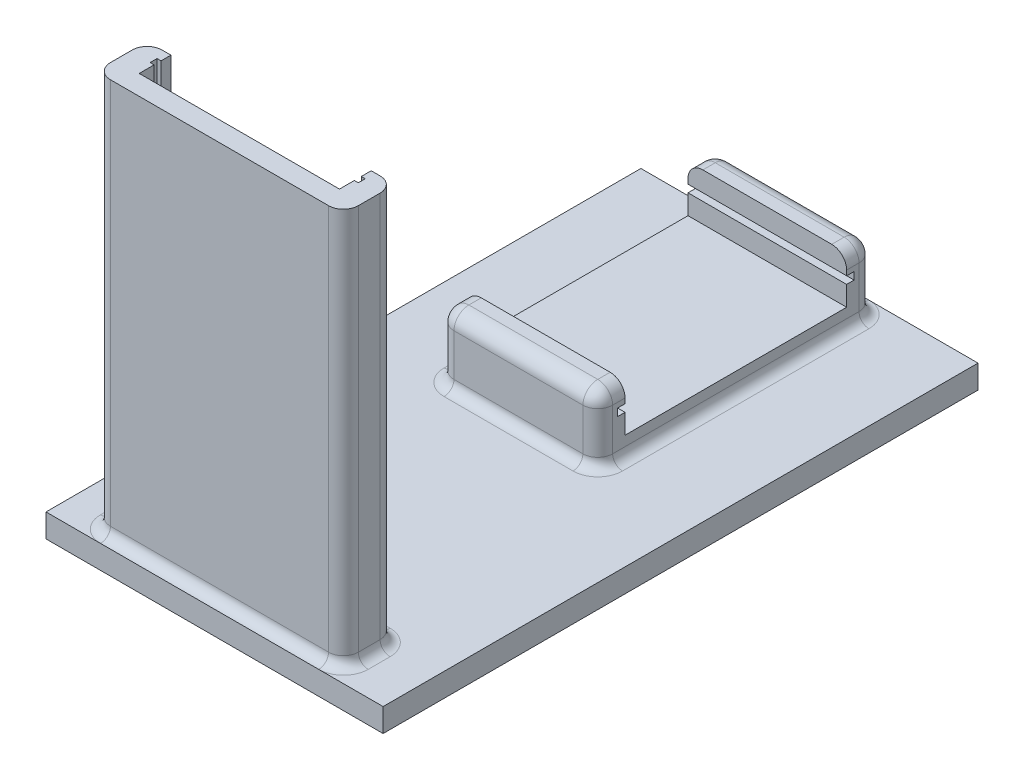
SolidWorks part; units mm, degrees
material "Melamine resin"
ref_plane "Front Plane" through (0, 0, 0) normal (0, 0, 1) x (1, 0, 0)
ref_plane "Top Plane" through (0, 0, 0) normal (0, 1, 0) x (1, 0, 0)
ref_plane "Right Plane" through (0, 0, 0) normal (1, 0, 0) x (0, 0, -1)
sketch "Sketch2" plane through (0, 0, 0) normal (0, 1, 0) x (1, 0, 0)
  line L1 (0, 0) -> (88.9, 0)
  line L2 (0, 0) -> (0, 152.4)
  line L3 (0, 152.4) -> (88.9, 152.4)
  line L10 (88.9, 152.4) -> (88.9, 0)
  dimension "D1" = 152.4
  dimension "D2" = 88.9
extrude "Boss-Extrude1" add sketch "Sketch2" along normal blind 5.9944 contours L3 L10 L1 L2
sketch "Sketch4" plane through (0, 5.9944, 0) normal (0, 1, 0) x (1, 0, 0)
  line L0 (0, 0) -> (0, 152.4) construction
  line L1 (0, 0) -> (88.9, 0) construction
  circle A0 centre (45.72, 109.8713) radius 2.7305
  circle A1 centre (45.72, 33.6713) radius 2.7305
  dimension "D3" = 5.461
  dimension "D4" = 5.461
  dimension "D1" = 76.2
  dimension "D2" = 45.72
  dimension "D5" = 33.6713
extrude "Cut-Extrude2" cut sketch "Sketch4" against normal through all both
sketch "Sketch5" plane through (0, 5.9944, 0) normal (0, 1, 0) x (1, 0, 0)
  line L0 (0, 152.4) -> (88.9, 152.4) construction
  line L1 (12.7, 15.748) -> (76.2, 15.748)
  line L2 (12.7, 15.748) -> (12.7, 2.54)
  line L3 (12.7, 2.54) -> (76.2, 2.54)
  line L4 (76.2, 15.748) -> (76.2, 2.54)
  line L5 (18.796, 7.62) -> (70.104, 7.62)
  line L6 (18.796, 7.62) -> (18.796, 15.748)
  line L7 (18.796, 15.748) -> (70.104, 15.748)
  line L8 (70.104, 7.62) -> (70.104, 15.748)
  line L9 (17.78, 13.208) -> (71.12, 13.208)
  line L10 (17.78, 13.208) -> (17.78, 11.43)
  line L11 (17.78, 11.43) -> (71.12, 11.43)
  line L12 (71.12, 13.208) -> (71.12, 11.43)
  line L13 (0, 0) -> (88.9, 0) construction
  point P16 (44.45, 152.4)
  point P17 (44.45, 15.748)
  dimension "D1" = 53.34
  dimension "D2" = 1.016
  dimension "D3" = 1.016
  dimension "D4" = 3.81
  dimension "D5" = 2.54
  dimension "D6" = 5.08
  dimension "D7" = 5.08
  dimension "D8" = 1.778
  dimension "D9" = 2.54
  dimension "D10" = 5.08
extrude "Boss-Extrude2" add sketch "Sketch5" along normal blind 101.6 contours L9 L12 L11 L8 L5 L6 L10 L1 L2 L3 L4 region at (44.45, 5.9944, -6.5828)
fillet "Fillet1" radius 3.81 4 edges at (12.7, 56.7944, -2.54) (12.7, 56.7944, -15.748) (76.2, 56.7944, -2.54) (76.2, 56.7944, -15.748)
fillet "Fillet2" radius 2.54 9 edges at (17.653, 5.9944, -15.748) (13.8159, 5.9944, -14.6321) (12.7, 5.9944, -9.144) (13.8159, 5.9944, -3.6559) (71.247, 5.9944, -15.748) (75.0841, 5.9944, -14.6321) (76.2, 5.9944, -9.144) (75.0841, 5.9944, -3.6559) (44.45, 5.9944, -2.54)
ref_plane "Plane1" through (44.45, 0, 0) normal (-1, 0, 0) x (0, 0, 1)
sketch "Sketch6" plane through (44.45, 0, 0) normal (-1, 0, 0) x (0, 0, 1)
  line L0 (0, 5.9944) -> (-152.4, 5.9944) construction
  line L1 (0, 5.9944) -> (-152.4, 5.9944)
  line L3 (-149.86, 5.9944) -> (-79.121, 5.9944)
  line L4 (-149.86, 5.9944) -> (-149.86, 23.1394)
  line L5 (-149.86, 23.1394) -> (-79.121, 23.1394)
  line L6 (-79.121, 5.9944) -> (-79.121, 23.1394)
  line L7 (-142.875, 23.1394) -> (-86.106, 23.1394)
  line L8 (-142.875, 23.1394) -> (-142.875, 11.0744)
  line L9 (-142.875, 11.0744) -> (-86.106, 11.0744)
  line L10 (-86.106, 23.1394) -> (-86.106, 11.0744)
  line L11 (-144.78, 18.0594) -> (-84.201, 18.0594)
  line L12 (-144.78, 18.0594) -> (-144.78, 16.1544)
  line L13 (-144.78, 16.1544) -> (-84.201, 16.1544)
  line L14 (-84.201, 18.0594) -> (-84.201, 16.1544)
  line L15 (-152.4, 5.9944) -> (-152.4, 0) construction
  dimension "D1" = 60.579
  dimension "D2" = 1.905
  dimension "D3" = 1.905
  dimension "D4" = 1.905
  dimension "D5" = 5.08
  dimension "D6" = 5.08
  dimension "D7" = 5.08
  dimension "D8" = 5.08
  dimension "D9" = 5.08
  dimension "D10" = 2.54
extrude "Boss-Extrude3" add sketch "Sketch6" along normal mid plane 40.64 contours L11 L14 L13 L10 L9 L8 L12 L5 L4 L1 L6 region at (44.45, 6.7223, -114.4905)
fillet "Fillet3" radius 3.81 2 edges at (44.45, 23.1394, -79.121) (44.45, 23.1394, -149.86)
fillet "Fillet6" radius 3.81 12 edges at (24.13, 23.1394, -84.5185) (24.13, 22.0235, -80.2369) (64.77, 23.1394, -84.5185) (64.77, 22.0235, -80.2369) (64.77, 23.1394, -144.4625) (64.77, 22.0235, -148.7441) (24.13, 23.1394, -144.4625) (24.13, 22.0235, -148.7441) (24.13, 12.6619, -79.121) (64.77, 12.6619, -79.121) (64.77, 12.6619, -149.86) (24.13, 12.6619, -149.86)
fillet "Fillet7" radius 2.54 8 edges at (25.2459, 5.9944, -80.2369) (44.45, 5.9944, -79.121) (63.6541, 5.9944, -80.2369) (64.77, 5.9944, -114.4905) (63.6541, 5.9944, -148.7441) (44.45, 5.9944, -149.86) (25.2459, 5.9944, -148.7441) (24.13, 5.9944, -114.4905)
sketch "Sketch7" plane through (0, 5.9944, 0) normal (0, 1, 0) x (1, 0, 0)
  line L0 (0, 0) -> (16.51, 0) construction
  line L1 (0, 152.4) -> (2.54, 152.4)
  line L2 (0, 152.4) -> (0, 0)
  line L3 (0, 0) -> (2.54, 0)
  line L4 (2.54, 152.4) -> (2.54, 0)
  dimension "D1" = 2.54
extrude "Cut-Extrude3" cut sketch "Sketch7" against normal through all both
equation "\"threaded_insert_hole\"=0.1472"
equation "\"th\"=1.25249"
